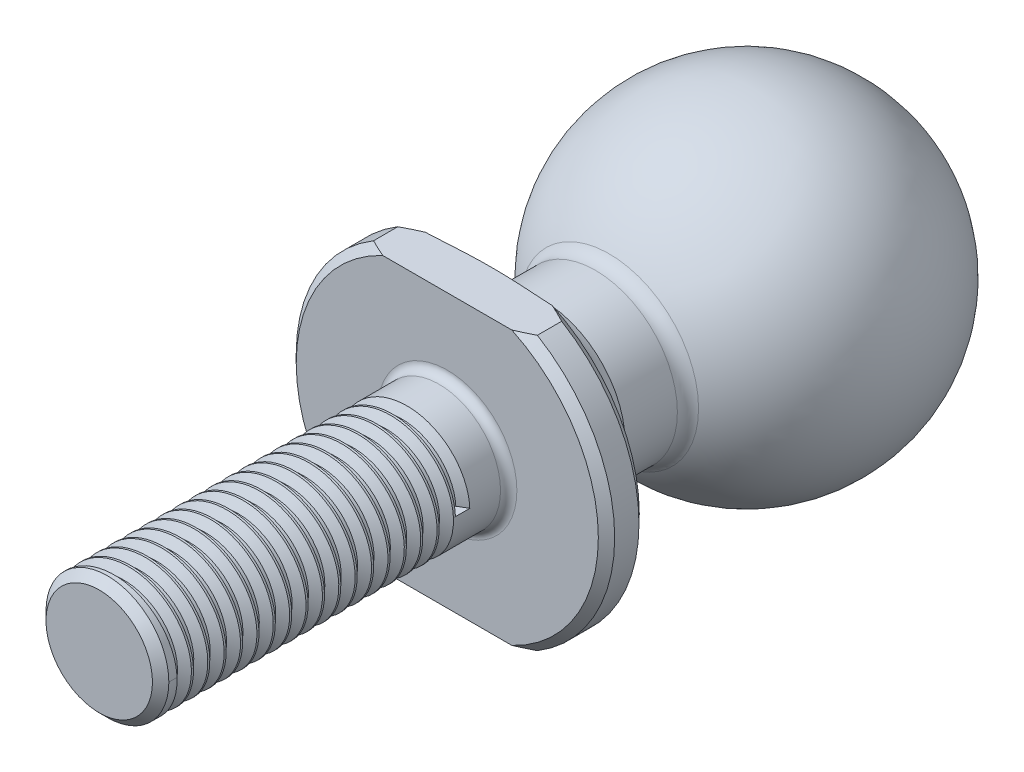
SolidWorks part; units mm, degrees
ref_plane "Front Plane" through (0, 0, 0) normal (0, 0, 1) x (1, 0, 0)
ref_plane "Top Plane" through (0, 0, 0) normal (0, 1, 0) x (1, 0, 0)
ref_plane "Right Plane" through (0, 0, 0) normal (1, 0, 0) x (0, 0, -1)
sketch "Sketch7" plane through (0, 0, 0) normal (0, 1, 0) x (1, 0, 0)
  line L0 (12.7, -31.522) -> (12.7, -21.997)
  line L1 (0, 0) -> (0, 21.997) construction
  line L2 (0, 21.997) -> (12.7, 21.997)
  line L4 (0, 25.4) -> (0, 52.6216) construction
  line L5 (12.7, -21.997) -> (12.7, -31.522)
  line L6 (0, 21.997) -> (0, -100.379)
  line L7 (0, -40.054) -> (24.6966, -40.054) construction
  line L8 (24.6966, -40.054) -> (24.6966, -46.404)
  line L9 (0, -100.379) -> (9.525, -100.379)
  line L10 (9.525, -100.379) -> (9.525, -46.404)
  line L11 (9.525, -46.404) -> (24.6966, -46.404)
  arc A0 (12.7, 21.997) -> (12.7, -21.997) centre (0, 0) cw
  arc A1 (24.6966, -40.054) -> (12.7, -31.522) centre (24.6966, -27.354) cw
  dimension "D1" = 25.4
  dimension "D7" = 12.7
  dimension "D2" = 52.6216
  dimension "D3" = 12.7
  dimension "D4" = 53.975
  dimension "D6" = 9.525
  dimension "D8" = 24.6966
  dimension "D9" = 6.35
  dimension "D10" = 9.525
revolve "Revolve19" add sketch "Sketch7" angle 360 about L1 region at (8.9822, 0, 27.9729)
sketch "Sketch10" plane through (0, 0, 46.404) normal (0, 0, 1) x (1, 0, 0)
  line L0 (-12.7, 21.1809) -> (12.7, 21.1809)
  line L1 (-12.7, -21.1809) -> (12.7, -21.1809)
  circle A0 centre (0, 0) radius 24.6966 construction
  arc A1 (-12.7, 21.1809) -> (12.7, 21.1809) centre (0, 0) cw
  dimension "D1" = 25.4
  dimension "D2" = 25.4
chamfer "Chamfer3" distance 1.27 angle 45 1 edges at (9.525, 0, 100.379)
fillet "Fillet1" radius 1.27 1 edges at (9.525, 0, 46.404)
thread "Thread2" pitch 2.54 method cut profile "Thread Profile2" start angle 0, offset 0, length 44.45, pitch 2.54, diameter 19.05
ref_plane "Plane2" through (-9.525, 0, 99.109) normal (0, -1, 0) x (-1, 0, 0)
sketch "Thread Profile2" plane through (-9.525, 0, 99.109) normal (0, -1, 0) x (-1, 0, 0)
  line L0 (0, 0) -> (0, 2.54) construction
  line L11 (0, 0) -> (0, 2.2225)
  line L12 (0, 2.2225) -> (-1.3748, 1.4287)
  line L13 (-1.3748, 1.4287) -> (-1.3748, 0.7937)
  line L15 (-1.3748, 0.7937) -> (0, 0)
  line L17 (-1.3748, 1.1112) -> (0, 1.1112) construction
  point P2 (0, 0)
  dimension "Pitch" = 2.54
  dimension "Profile_Angle" = 60
  dimension "Profile_Land" = 0.635
  dimension "Profile_Height" = 1.3748
fillet "Fillet2" radius 1.27 1 edges at (12.7, 0, -21.997)
fillet "Fillet3" radius 2.54 1 edges at (12.7, 0, 21.997)
sketch "Sketch23" plane through (0, 0, 46.404) normal (0, 0, 1) x (1, 0, 0)
extrude "Cut-Extrude8" cut sketch "Sketch10" against normal blind 10 contours L0 A1
sketch "Sketch35" plane through (0, 0, 46.404) normal (0, 0, 1) x (1, 0, 0)
  line L0 (12.7, -21.1809) -> (-12.7, -21.1809)
  arc A0 (-12.7, 21.1809) -> (12.7, 21.1809) centre (0, 0) ccw construction
  arc A1 (12.7, -21.1809) -> (-12.7, -21.1809) centre (0, 0) cw
  dimension "D1" = 25.4
extrude "Cut-Extrude9" cut sketch "Sketch35" against normal blind 10 contours A1 L0
chamfer "Chamfer4" distance 1.27 angle 45 2 edges at (-24.6966, 0, 46.404) (24.6966, 0, 46.404)
chamfer "Chamfer5" distance 1.27 angle 46 2 edges at (-24.6966, 0, 40.054) (24.6966, 0, 40.054) first distance on face at (0, 0, 27.4749)
